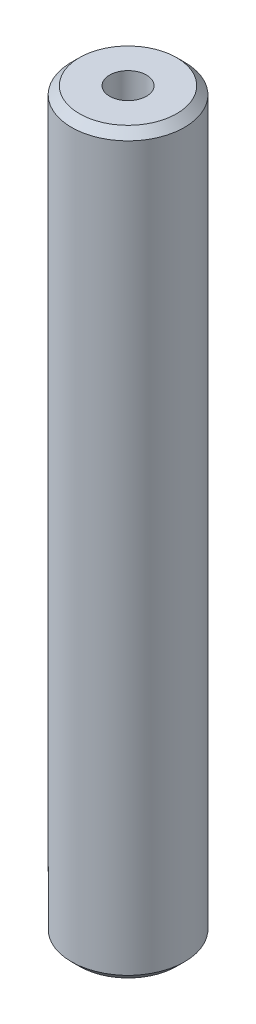
SolidWorks part; units mm, degrees
ref_plane "Front Plane" through (0, 0, 0) normal (0, 0, 1) x (1, 0, 0)
ref_plane "Top Plane" through (0, 0, 0) normal (0, 1, 0) x (1, 0, 0)
ref_plane "Right Plane" through (0, 0, 0) normal (1, 0, 0) x (0, 0, -1)
sketch "Sketch1" plane through (0, 0, 0) normal (0, 1, 0) x (1, 0, 0)
  circle A0 centre (0, 0) radius 27.5
  dimension "SHAFT_OD" = 55
extrude "Boss-Extrude1" add sketch "Sketch1" along normal blind 359.3326
sketch "Sketch2" plane through (0, 0, 0) normal (0, 1, 0) x (1, 0, 0)
  circle A0 centre (0, 0) radius 8.9596
  dimension "BORE_D" = 17.9193
extrude "Cut-Extrude1" cut sketch "Sketch2" along normal through all
chamfer "Chamfer1" distance 3.8442 angle 45 2 edges at (0, 359.3326, 27.5) (0, 0, 27.5)
